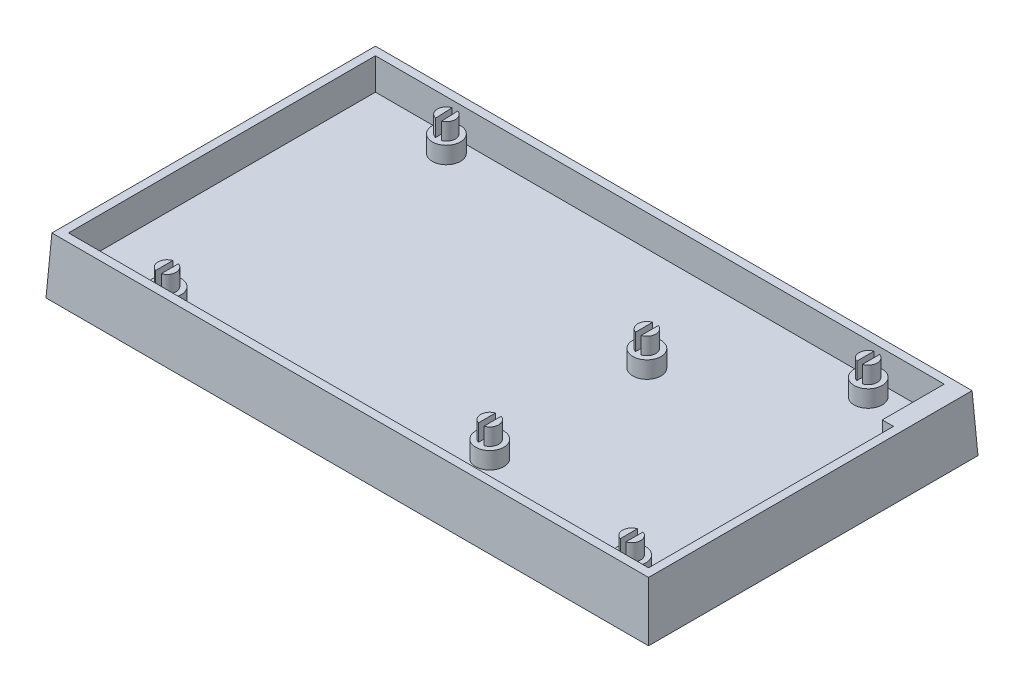
SolidWorks part; units mm, degrees
note: The reader was unsure of these and kept them because the rebuilt part matched: shared geometry of "Sketch2<5>", "Sketch10<3>".
ref_plane "Front Plane" through (0, 0, 0) normal (0, 0, 1) x (1, 0, 0)
ref_plane "Top Plane" through (0, 0, 0) normal (0, 1, 0) x (1, 0, 0)
ref_plane "Right Plane" through (0, 0, 0) normal (1, 0, 0) x (0, 0, -1)
sketch "Sketch2" plane through (0, 0, 0) normal (0, 1, 0) x (1, 0, 0)
  line L0 (-2, -2) -> (-2, 56.5)
  line L1 (0, 0) -> (103, 0)
  line L2 (0, 0) -> (0, 54.5)
  line L3 (0, 54.5) -> (103, 54.5)
  line L4 (103, 0) -> (103, 54.5)
  line L5 (-2, 56.5) -> (105, 56.5)
  line L6 (105, -2) -> (105, 56.5)
  line L7 (-2, -2) -> (105, -2)
  line L8 (101, 43.5) -> (103, 41.5)
  line L9 (105, -2) -> (101, -2)
  line L10 (105, -2) -> (105, 1)
  line L11 (105, 1) -> (101, 1)
  line L12 (101, -2) -> (101, 1)
  line L13 (105, 56.5) -> (101, 56.5)
  line L14 (105, 56.5) -> (105, 43.5)
  line L15 (105, 43.5) -> (101, 43.5)
  line L16 (101, 56.5) -> (101, 43.5)
  line L17 (101, 1) -> (103, 3)
  dimension "D1" = 103
  dimension "D2" = 54.5
  dimension "D4" = 4
  dimension "D5" = 3
  dimension "D6" = 4
  dimension "D7" = 13
  dimension "D8" = 15
  dimension "D9" = 5
  dimension "D3" = 2
extrude "Boss-Extrude1" add sketch "Sketch2" along normal blind 10 draft 3 contours L12 L17 L4 L8 L16 L3 L2 L1 | L16 L5 L0 L7 L12 L1 L2 L3 | L3 L16 L15 L4 | L5 L16 L3 L4 L15 L6 | L6 L15 L4 L11 | L12 L7 L6 L11 L4 L1 | L12 L1 L4 L11 | L4 L15 L8 | L17 L11 L4
extrude "Cut-Extrude1" cut sketch "Sketch2<5>" against normal blind 5.6 from surface at 10 contours L12 L17 L4 L8 L16 L3 L2 L1 | L4 L15 L8 | L17 L11 L4 | L12 L1 L4 L11
sketch "Sketch2<5>" plane through (0, 0, 0) normal (0, 1, 0) x (1, 0, 0) same geometry as "Sketch2"
sketch "Sketch8" plane through (0, 0, 0) normal (0, -1, 0) x (1, 0, 0)
  line L4 (105, -56.5) -> (105, 2)
  line L5 (105, 2) -> (-2, 2)
  line L6 (-2, 2) -> (-2, -56.5)
  line L7 (-2, -56.5) -> (105, -56.5)
  line L8 (105, -56.5) -> (105, 2)
  line L9 (105, 2) -> (-2, 2)
  line L10 (-2, 2) -> (-2, -56.5)
  line L11 (-2, -56.5) -> (105, -56.5)
  dimension "D1" = 0
extrude "Boss-Extrude2" add sketch "Sketch8" along normal blind 5 draft 45
sketch "Sketch9" plane through (0, -5, 0) normal (0, -1, 0) x (1, 0, 0)
  line L0 (51.5, 2) -> (51.5, -56.5) construction
  line L1 (24.45, -17.2) -> (28.55, -17.2)
  line L2 (24.45, -17.2) -> (24.45, -37.3)
  line L3 (24.45, -37.3) -> (28.55, -37.3)
  line L4 (28.55, -17.2) -> (28.55, -37.3)
  line L5 (-2, 2) -> (105, 2) construction
  line L6 (-2, -56.5) -> (105, -56.5) construction
  line L7 (26.5, -27.25) -> (51.5, -27.25) construction
  line L8 (26.5, -17.2) -> (26.5, -37.3) construction
  line L9 (78.55, -37.3) -> (74.45, -37.3)
  line L10 (74.45, -17.2) -> (74.45, -37.3)
  line L11 (78.55, -17.2) -> (74.45, -17.2)
  line L12 (78.55, -17.2) -> (78.55, -37.3)
  point P10 (26.5, -27.25)
  point P11 (51.5, -27.25)
  dimension "D1" = 4.1
  dimension "D2" = 20.1
  dimension "D3" = 25
extrude "Boss-Extrude3" add sketch "Sketch9" along normal blind 5
chamfer "Chamfer1" distance 2 angle 45 2 edges at (26.5, -10, -17.2) (76.5, -10, -17.2)
sketch "Sketch10" plane through (0, 4.4, 0) normal (0, 1, 0) x (1, 0, 0)
  line L0 (15.7, 53) -> (15.85, 49.5) construction
  line L1 (90.6, 53) -> (90.6, 49.8) construction
  line L2 (96.9, 4.7) -> (96.9, 0.6) construction
  line L3 (66.5, 9.9) -> (66.5, 6.7) construction
  line L4 (14.4, 4.7) -> (14.4, 1.5) construction
  line L5 (66.5, 37.8) -> (66.5, 34.6) construction
  line L6 (15.2005, 52.9786) -> (15.3505, 49.4786)
  line L7 (90.1, 53) -> (90.1, 49.8)
  line L8 (66, 9.9) -> (66, 6.7)
  line L9 (13.9, 4.7) -> (13.9, 1.5)
  line L10 (16.1995, 53.0214) -> (16.3495, 49.5214)
  line L11 (91.1, 53) -> (91.1, 49.8)
  line L12 (67, 9.9) -> (67, 6.7)
  line L13 (14.9, 4.7) -> (14.9, 1.5)
  line L14 (66, 37.8) -> (66, 34.6)
  line L15 (96.4, 4.7) -> (96.4, 0.6)
  line L16 (67, 37.8) -> (67, 34.6)
  line L17 (97.4, 4.7) -> (97.4, 0.6)
  circle A0 centre (15.7, 51.4) radius 2.5
  circle A1 centre (90.6, 51.4) radius 2.5
  circle A2 centre (14.4, 3.1) radius 2.5
  circle A5 centre (66.5, 36.2) radius 2.5
  circle A6 centre (96.9, 3.1) radius 2.5
  circle A7 centre (66.5, 8.3) radius 2.5
  circle A8 centre (96.9, 3.1) radius 1.6 construction
  circle A9 centre (66.5, 8.3) radius 1.6 construction
  circle A10 centre (14.4, 3.1) radius 1.6 construction
  circle A11 centre (66.5, 36.2) radius 1.6 construction
  circle A12 centre (90.6, 51.4) radius 1.6 construction
  circle A13 centre (15.7, 51.4) radius 1.6 construction
  circle A14 centre (96.9, 3.1) radius 1.6
  circle A15 centre (66.5, 8.3) radius 1.6
  circle A16 centre (14.4, 3.1) radius 1.6
  circle A17 centre (66.5, 36.2) radius 1.6
  circle A18 centre (90.6, 51.4) radius 1.6
  circle A19 centre (15.7, 51.4) radius 1.6
  dimension "D1" = 5
  dimension "D2" = 0.5
  dimension "D3" = 0.5
  dimension "D4" = 0.5
  dimension "D5" = 0.5
extrude "Boss-Extrude4" add sketch "Sketch10" along normal blind 3
extrude "Boss-Extrude5" add sketch "Sketch10<3>" along normal blind 3 from surface at 3 contours L10 A19 | L6 A19 | L11 A18 | L7 A18 | L13 A16 | L9 A16 | L16 A17 | L14 A17 | L12 A15 | L8 A15 | L17 A14 | L15 A14 starting at face at (15.7, 7.4, -48.9)
sketch "Sketch10<3>" plane through (0, 4.4, 0) normal (0, 1, 0) x (1, 0, 0) same geometry as "Sketch10"
